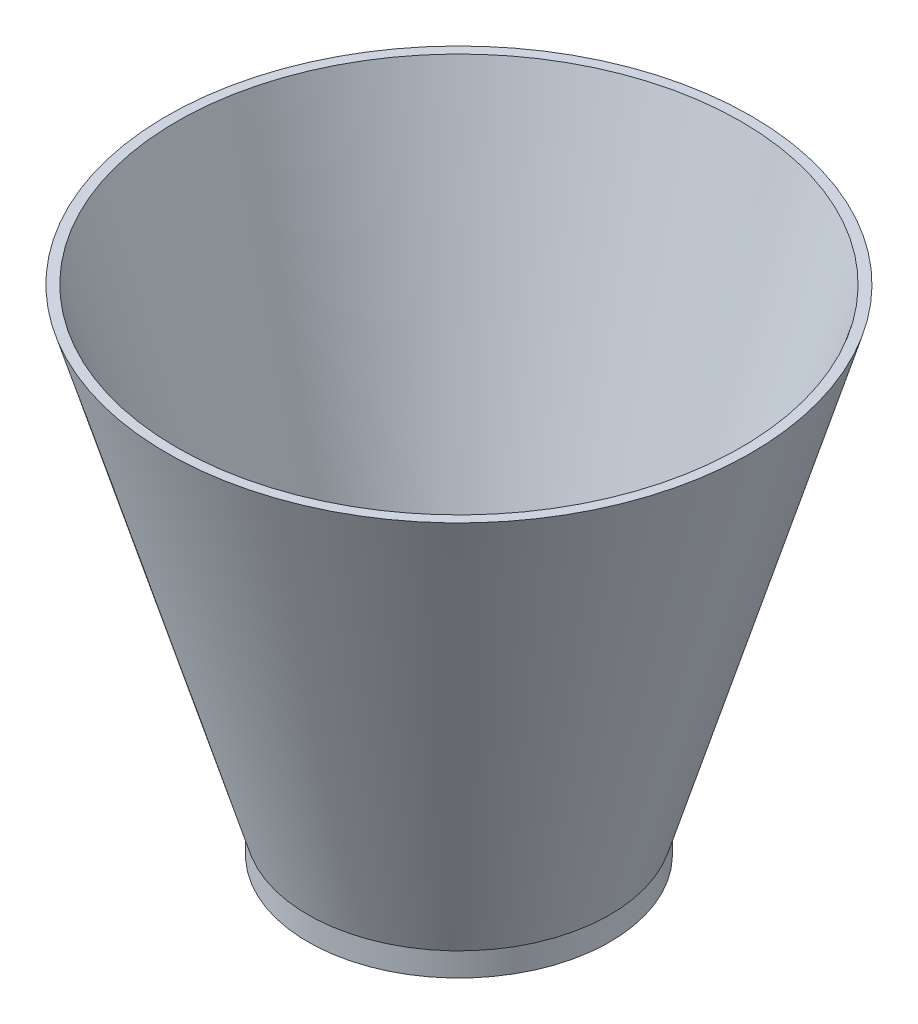
SolidWorks part; units mm, degrees
ref_plane "Front Plane" through (0, 0, 0) normal (0, 0, 1) x (1, 0, 0)
ref_plane "Top Plane" through (0, 0, 0) normal (0, 1, 0) x (1, 0, 0)
ref_plane "Right Plane" through (0, 0, 0) normal (1, 0, 0) x (0, 0, -1)
sketch "Sketch1" plane through (0, 0, 0) normal (0, 0, 1) x (1, 0, 0)
  line L0 (-30, 0) -> (-60, 100)
  line L1 (0, 0) -> (0, 68.8325) construction
  line L2 (-32.0881, 0) -> (-62.0881, 100)
  line L3 (-60, 100) -> (-62.0881, 100)
  line L4 (-30, 0) -> (-32.0881, 0)
  line L5 (-31.9157, -0.5747) -> (-61.9157, 99.4253) construction
  dimension "D1" = 30
  dimension "D2" = 60
  dimension "D3" = 100
  dimension "D4" = 0
  dimension "D5" = 2
revolve "Revolve1" add sketch "Sketch1" angle 360 about L1
sketch "Sketch2" plane through (0, 0, 0) normal (0, -1, 0) x (1, 0, 0)
  circle A0 centre (0, 0) radius 32.0881
  circle A1 centre (0, 0) radius 30
extrude "Boss-Extrude1" add sketch "Sketch2" along normal blind 5
